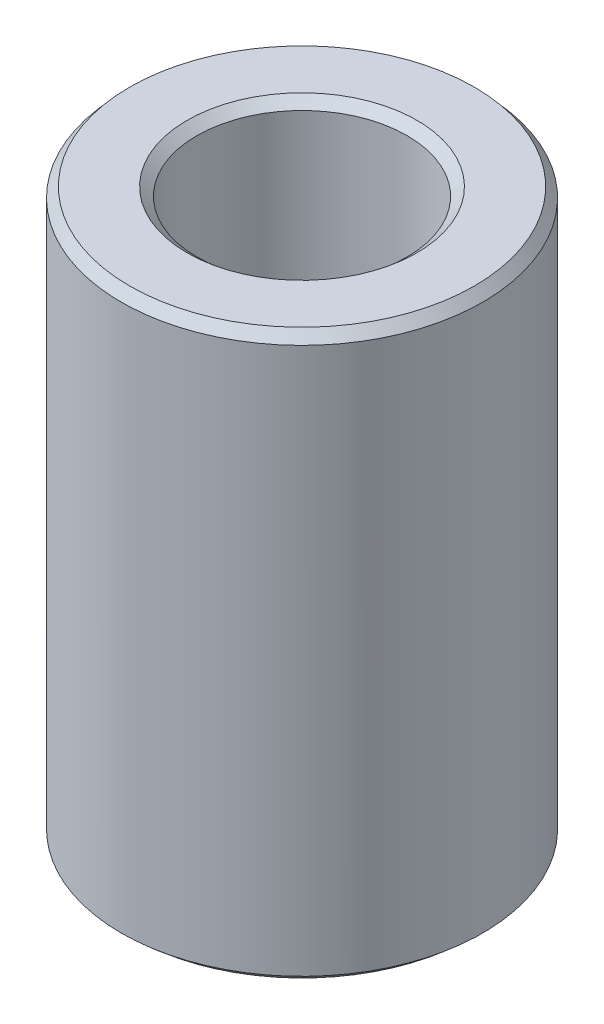
SolidWorks part; units mm, degrees
ref_plane "Front Plane" through (0, 0, 0) normal (0, 0, 1) x (1, 0, 0)
ref_plane "Top Plane" through (0, 0, 0) normal (0, 1, 0) x (1, 0, 0)
ref_plane "Right Plane" through (0, 0, 0) normal (1, 0, 0) x (0, 0, -1)
sketch "Sketch1" plane through (0, 0, 0) normal (0, 1, 0) x (1, 0, 0)
  circle A0 centre (0, 0) radius 15
  dimension "SLEEVE_OD" = 30
extrude "Boss-Extrude1" add sketch "Sketch1" along normal blind 46.8626
sketch "Sketch2" plane through (0, 0, 0) normal (0, 1, 0) x (1, 0, 0)
  circle A0 centre (0, 0) radius 8.7233
  dimension "BORE_D" = 17.4465
extrude "Cut-Extrude1" cut sketch "Sketch2" along normal through all
chamfer "Chamfer1" distance 0.8114 angle 40.708 4 edges at (0, 46.8626, 8.7233) (0, 0, 8.7233) (0, 0, 15) (0, 46.8626, 15) first distance on face at (0, 46.8626, 8.7233) first distance on face at (0, 0, 8.7233) first distance on face at (0, 46.8626, 15)
